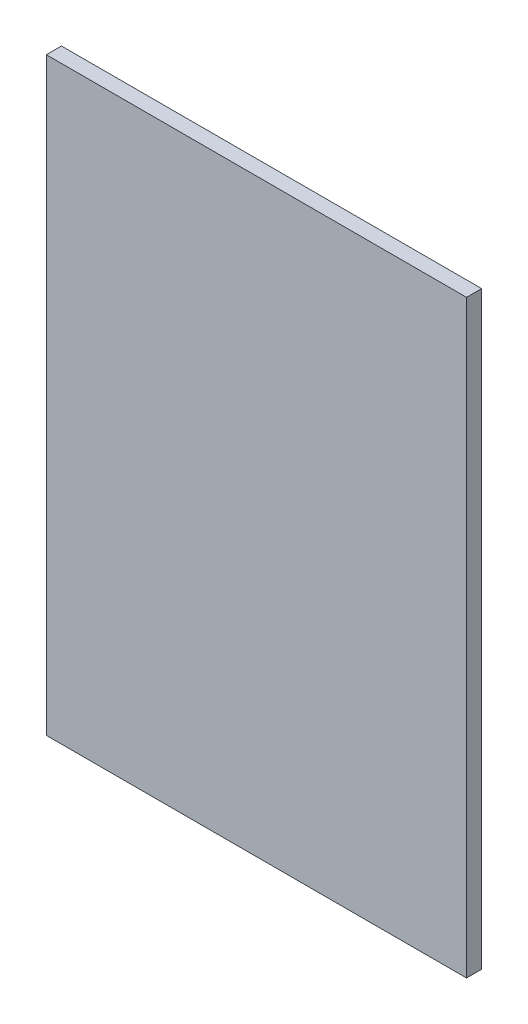
SolidWorks part; units mm, degrees
ref_plane "Alzado" through (0, 0, 0) normal (0, 0, 1) x (1, 0, 0)
ref_plane "Planta" through (0, 0, 0) normal (0, 1, 0) x (1, 0, 0)
ref_plane "Vista lateral" through (0, 0, 0) normal (1, 0, 0) x (0, 0, -1)
sketch "Croquis1" plane through (0, 0, 0) normal (0, 0, 1) x (1, 0, 0)
  line L1 (-69.5, -97.5) -> (69.5, -97.5)
  line L2 (-69.5, -97.5) -> (-69.5, 97.5)
  line L3 (-69.5, 97.5) -> (69.5, 97.5)
  line L4 (69.5, -97.5) -> (69.5, 97.5)
  line L5 (-69.5, -97.5) -> (69.5, 97.5) construction
  line L6 (-69.5, 97.5) -> (69.5, -97.5) construction
  point P0 (0, 0)
  dimension "D1" = 139
  dimension "D2" = 195
extrude "Saliente-Extruir1" add sketch "Croquis1" along normal blind 5
